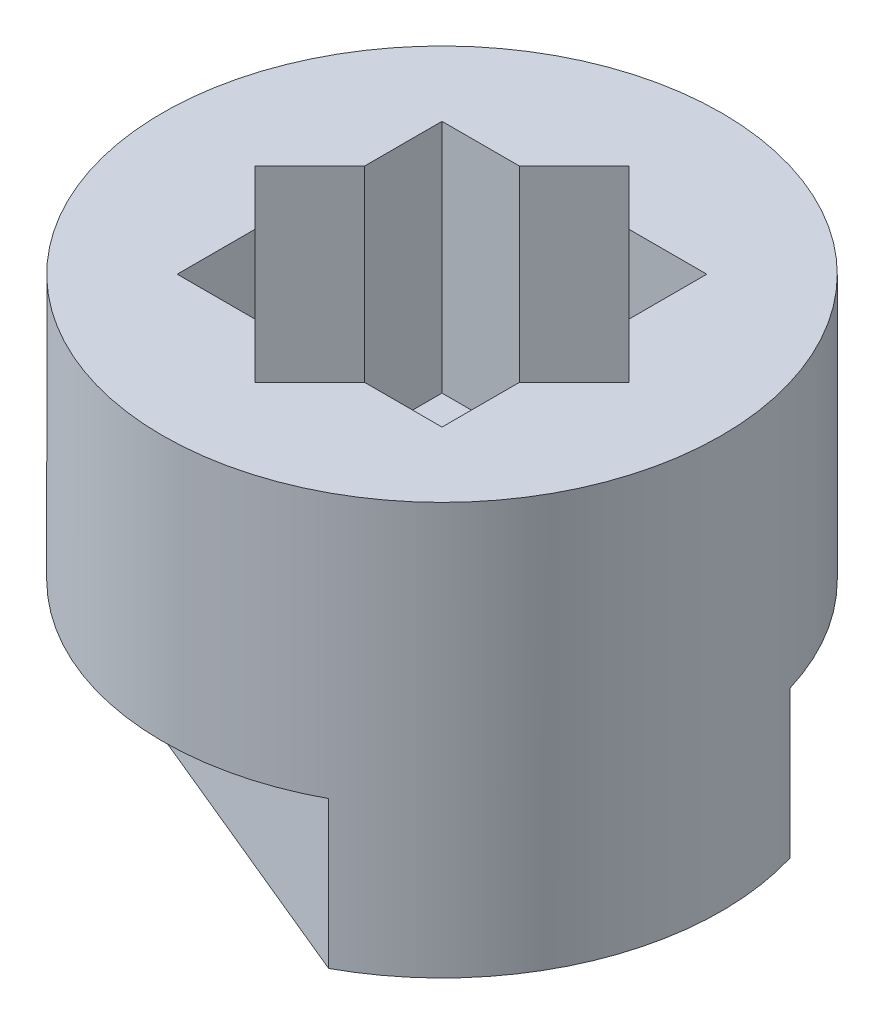
SolidWorks part; units mm, degrees
material "ПК/АБС"
ref_plane "Спереди" through (0, 0, 0) normal (0, 0, 1) x (1, 0, 0)
ref_plane "Сверху" through (0, 0, 0) normal (0, 1, 0) x (1, 0, 0)
ref_plane "Справа" through (0, 0, 0) normal (1, 0, 0) x (0, 0, -1)
sketch "Эскиз1" plane through (0, 0, 0) normal (0, 1, 0) x (1, 0, 0)
  circle A0 centre (0, 0) radius 4.75
  dimension "D1" = 9.5
extrude "Бобышка-Вытянуть1" add sketch "Эскиз1" along normal blind 7
sketch "Эскиз2" plane through (0, 7, 0) normal (0, 1, 0) x (1, 0, 0)
  line L1 (-3.182, 0) -> (-2.25, -0.932)
  line L2 (-3.182, 0) -> (-2.25, 0.932)
  line L3 (0, 3.182) -> (0.932, 2.25)
  line L4 (0, -3.182) -> (0.932, -2.25)
  line L5 (-3.182, 0) -> (3.182, 0) construction
  line L6 (0, 3.182) -> (0, -3.182) construction
  line L7 (-2.25, -2.25) -> (-0.932, -2.25)
  line L8 (-2.25, -2.25) -> (-2.25, -0.932)
  line L9 (-2.25, 2.25) -> (-0.932, 2.25)
  line L10 (2.25, -2.25) -> (2.25, -0.932)
  line L11 (-2.25, -2.25) -> (2.25, 2.25) construction
  line L12 (-2.25, 2.25) -> (2.25, -2.25) construction
  line L13 (-0.932, 2.25) -> (0, 3.182)
  line L15 (2.25, 0.932) -> (3.182, 0)
  line L16 (2.25, -0.932) -> (3.182, 0)
  line L18 (-0.932, -2.25) -> (0, -3.182)
  line L21 (-2.25, 0.932) -> (-2.25, 2.25)
  line L23 (0.932, 2.25) -> (2.25, 2.25)
  line L24 (2.25, 0.932) -> (2.25, 2.25)
  line L26 (0.932, -2.25) -> (2.25, -2.25)
  point P0 (0, 0)
  point P6 (0, 0)
  dimension "D1" = 4.5
extrude "Вырез-Вытянуть1" cut sketch "Эскиз2" against normal blind 4
sketch "Эскиз3" plane through (0, 0, 0) normal (0, -1, 0) x (1, 0, 0)
  circle A0 centre (0, 0) radius 1.85
  dimension "D1" = 3.7
extrude "Вырез-Вытянуть2" cut sketch "Эскиз3" against normal through all contours A0 region at (0, 0, 0)
sketch "Эскиз4" plane through (0, 0, 0) normal (0, -1, 0) x (1, 0, 0)
  line L0 (-4.5504, 1.3623) -> (2.2543, 4.181)
  line L1 (-2.2543, -4.181) -> (4.5504, -1.3623)
  line L2 (-4.5504, 1.3623) -> (4.5504, -1.3623) construction
  line L3 (-3.182, 0) -> (-2.25, 0.932) construction
  circle A0 centre (0, 0) radius 4.75 construction
  circle A1 centre (0, 0) radius 2.5
  circle M1 centre (0, 0) radius 1.85
  circle M2 centre (0, 0) radius 4.75
  dimension "D2" = 5
  dimension "D1" = 6
  dimension "D3" = 22.5
extrude "Вырез-Вытянуть4" [suppressed] cut sketch "Эскиз4" against normal blind 2 contours A1 M1 | A1 L2 M1
extrude "Вырез-Вытянуть7" cut sketch "Эскиз4<3>" against normal offset from surface (2.5 mm away) 4.5 contours L0 M2 | L1 M2 region at (-1.4207, 0, 3.4298) region at (1.4207, 0, -3.4298) up to face at (0, 7, 0)
sketch "Эскиз4<3>" plane through (0, 0, 0) normal (0, -1, 0) x (1, 0, 0) same geometry as "Эскиз4"
